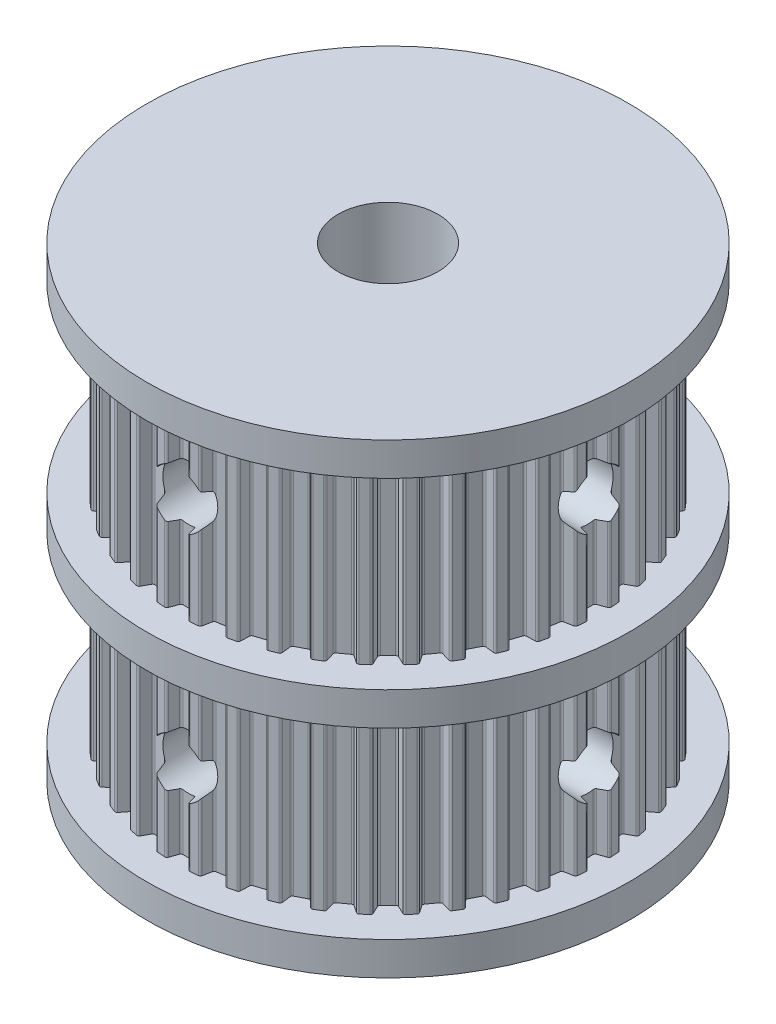
SolidWorks part; units mm, degrees
ref_plane "Front Plane" through (0, 0, 0) normal (0, 0, 1) x (1, 0, 0)
ref_plane "Top Plane" through (0, 0, 0) normal (0, 1, 0) x (1, 0, 0)
ref_plane "Right Plane" through (0, 0, 0) normal (1, 0, 0) x (0, 0, -1)
sketch "草圖1" plane through (0, 0, 0) normal (0, 1, 0) x (1, 0, 0)
  circle A0 centre (0, 0) radius 12.68
  dimension "D1" = 25.36
extrude "填料-伸長1" add sketch "草圖1" along normal mid plane 24 contours A0
sketch "草圖2" plane through (0, -12, 0) normal (0, -1, 0) x (1, 0, 0)
  line L0 (0, 12.68) -> (0, 0) construction
  line L1 (0, 11.99) -> (-0.42, 11.99)
  line L2 (-0.42, 11.99) -> (-0.6648, 12.6626)
  line L3 (0, 11.99) -> (0.42, 11.99)
  line L4 (0.42, 11.99) -> (0.6648, 12.6626)
  circle A0 centre (0, 0) radius 12.68 construction
  arc A1 (-0.6648, 12.6626) -> (0.6648, 12.6626) centre (0, 0) cw
  circle M7 centre (0, 0) radius 12.68
  dimension "D1" = 0.69
  dimension "D2" = 0.84
  dimension "D3" = 40
extrude "除料-伸長1" cut sketch "草圖2" against normal through all contours L0 A1 L2 L1 | L0 L3 L4 M7 region at (0.2753, -12, 12.3582) region at (-0.2753, -12, 12.3582)
fillet "圓角1" radius 0.13 4 edges at (-0.6648, 0, 12.6626) (0.6648, 0, 12.6626) (0.42, 0, 11.99) (-0.42, 0, 11.99)
pattern_circular "環狀複製排列1" count 40 over 360 about axis through (0, 12, 0) along (0, -1, 0) of "圓角1", "除料-伸長1"
sketch "草圖3" plane through (0, 12, 0) normal (0, 1, 0) x (1, 0, 0)
  circle A0 centre (0, 0) radius 14.5
  dimension "D1" = 29
extrude "填料-伸長2" add sketch "草圖3" along normal blind 2
sketch "草圖4" plane through (0, -12, 0) normal (0, -1, 0) x (1, 0, 0)
  circle A0 centre (0, 0) radius 14.5
  circle A1 centre (0, 0) radius 14.5 construction
extrude "填料-伸長3" add sketch "草圖4" along normal blind 2
sketch "草圖10" plane through (0, -14, 0) normal (0, -1, 0) x (1, 0, 0)
  circle A0 centre (0, 0) radius 14.5
  dimension "D1" = 29
extrude "填料-伸長4" add sketch "草圖10" along normal mid plane 2 from offset 14 offset against normal yes
sketch "草圖5" plane through (0, -14, 0) normal (0, -1, 0) x (1, 0, 0)
  circle A0 centre (0, 0) radius 3
  dimension "D1" = 6
extrude "除料-伸長2" cut sketch "草圖5" against normal through all
hole_wizard "M4x0.7 螺紋孔1" positions "草圖8" profile "草圖9" tap size "M4x0.7" standard "Ansi Metric" end condition through all
sketch "草圖8" plane through (0, 0, 0) normal (0, 0, 1) x (1, 0, 0)
  line L0 (0, -7) -> (0, 0) construction
  line L1 (0, 0) -> (0, 7) construction
  point P3 (0, -7)
  point P5 (0, 7)
  dimension "D1" = 7
  dimension "D2" = 7
sketch "草圖9" plane through (0, -7, 0) normal (1, 0, 0) x (0, 1, 0)
  line L0 (0, 0) -> (0, 14.5)
  line L1 (0, 14.5) -> (1.65, 14.5)
  line L2 (1.65, 14.5) -> (1.65, 0)
  line L5 (1.65, 0) -> (0, 0)
  line L11 (0, -6.35) -> (0, 107.95) construction
  dimension "貫穿螺孔鑽直徑" = 3.3
  dimension "貫穿螺孔鑽深度" = 14.5
pattern_circular "環狀複製排列2" count 2 over 90 about axis through (0, 14, 0) along (0, -1, 0) of "M4x0.7 螺紋孔1" reverse direction yes
